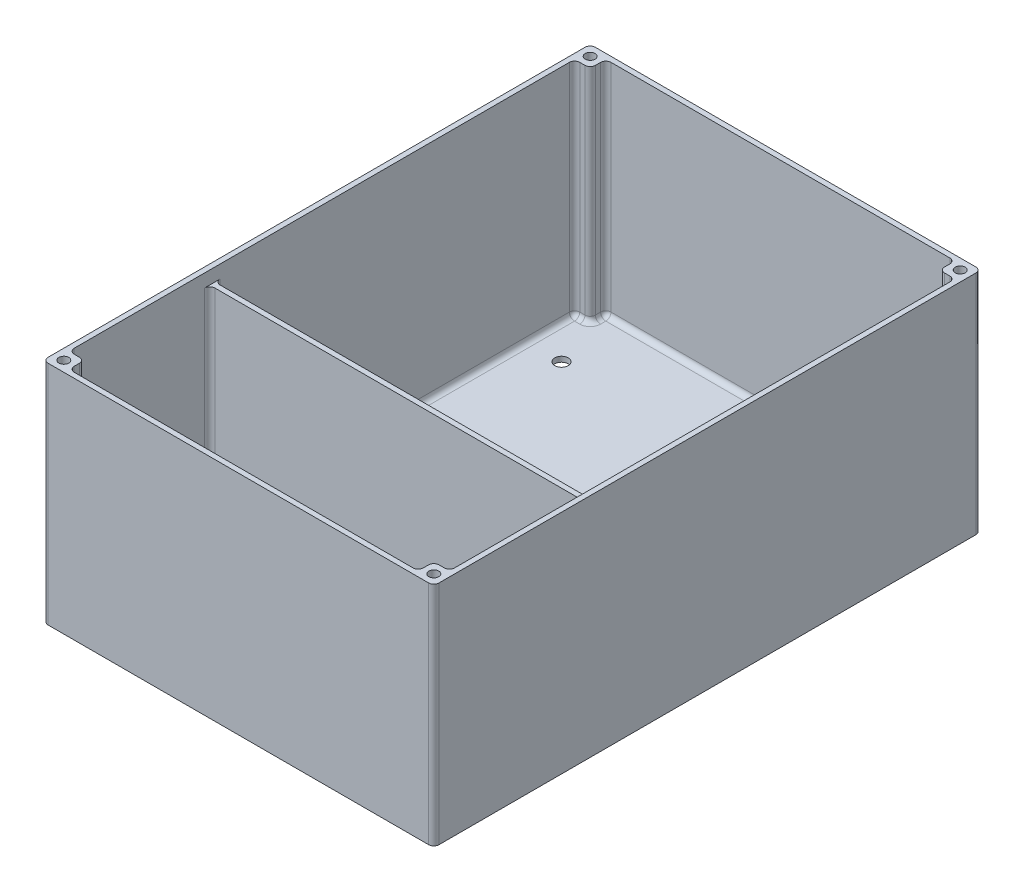
SolidWorks part; units mm, degrees
ref_plane "Front Plane" through (0, 0, 0) normal (0, 0, 1) x (1, 0, 0)
ref_plane "Top Plane" through (0, 0, 0) normal (0, 1, 0) x (1, 0, 0)
ref_plane "Right Plane" through (0, 0, 0) normal (1, 0, 0) x (0, 0, -1)
sketch "Sketch1" plane through (0, 0, 0) normal (0, 1, 0) x (1, 0, 0)
  line L1 (0, 0) -> (150, 0)
  line L2 (0, 0) -> (0, 210)
  line L3 (0, 210) -> (150, 210)
  line L4 (150, 0) -> (150, 210)
  dimension "D1" = 150
  dimension "D2" = 210
extrude "Boss-Extrude3" add sketch "Sketch1" along normal blind 2
sketch "Sketch3" plane through (0, 2, 0) normal (0, 1, 0) x (1, 0, 0)
  line L5 (0, 210) -> (150, 210)
  line L6 (0, 210) -> (0, 0)
  line L7 (0, 0) -> (150, 0)
  line L8 (2, 208) -> (2, 2)
  line L9 (2, 2) -> (148, 2)
  line L10 (148, 2) -> (148, 208)
  line L11 (148, 208) -> (2, 208)
  line L12 (2, 202) -> (2, 8)
  line L13 (8, 2) -> (142, 2)
  line L14 (148, 8) -> (148, 202)
  line L15 (142, 208) -> (8, 208)
  line L16 (150, 210) -> (150, 0)
  line L19 (2, 202) -> (8, 202)
  line L20 (8, 208) -> (8, 202)
  line L23 (148, 202) -> (142, 202)
  line L24 (142, 208) -> (142, 202)
  line L27 (2, 8) -> (8, 8)
  line L28 (8, 2) -> (8, 8)
  line L31 (148, 8) -> (142, 8)
  line L32 (142, 2) -> (142, 8)
  dimension "D2" = 6
  dimension "D1" = 2
extrude "Boss-Extrude4" add sketch "Sketch3" along normal blind 85
ref_plane "Plane1" through (75, 0, 0) normal (1, 0, 0) x (0, 0, -1)
ref_plane "Plane2" through (0, 0, -105) normal (0, 0, 1) x (1, 0, 0)
fillet "Fillet1" radius 2 16 edges at (150, 43.5, -210) (150, 43.5, 0) (0, 43.5, 0) (0, 43.5, -210) (2, 44.5, -8) (8, 44.5, -8) (8, 44.5, -2) (142, 44.5, -2) (142, 44.5, -8) (148, 44.5, -8) (148, 44.5, -202) (142, 44.5, -202) (142, 44.5, -208) (8, 44.5, -202) (8, 44.5, -208) (2, 44.5, -202)
sketch "Sketch4" plane through (0, 87, 0) normal (0, 1, 0) x (1, 0, 0)
  line L0 (4, 206) -> (4, 210) construction
  line L1 (148, 210) -> (2, 210) construction
  line L2 (4, 206) -> (0, 206) construction
  line L3 (0, 208) -> (0, 2) construction
  line L4 (75, -47.85) -> (75, 47.85) construction
  line L5 (146, 206) -> (150, 206) construction
  line L6 (146, 206) -> (146, 210) construction
  line L7 (-47.85, 105) -> (47.85, 105) construction
  line L8 (146, 4) -> (146, 0) construction
  line L9 (146, 4) -> (150, 4) construction
  line L10 (4, 4) -> (0, 4) construction
  line L11 (4, 4) -> (4, 0) construction
  circle A0 centre (4, 206) radius 1.9
  circle A1 centre (146, 206) radius 1.9
  circle A2 centre (146, 4) radius 1.9
  circle A3 centre (4, 4) radius 1.9
  dimension "D3" = 3.8
  dimension "D1" = 4
  dimension "D2" = 4
extrude "Cut-Extrude1" cut sketch "Sketch4" against normal blind 10
sketch "Sketch5" plane through (0, 2, 0) normal (0, 1, 0) x (1, 0, 0)
  line L0 (15, 184) -> (135, 184) construction
  line L1 (135, 184) -> (135, 76) construction
  line L2 (135, 76) -> (15, 76) construction
  line L3 (15, 76) -> (15, 184) construction
  line L5 (15, 184) -> (2, 184) construction
  line L6 (2, 200) -> (2, 10) construction
  line L7 (135, 184) -> (148, 184) construction
  line L8 (148, 10) -> (148, 200) construction
  circle A0 centre (15, 184) radius 2.6
  circle A1 centre (135, 184) radius 2.6
  circle A2 centre (135, 76) radius 2.6
  circle A3 centre (15, 76) radius 2.6
  dimension "D5" = 5.2
  dimension "D1" = 120
  dimension "D2" = 108
  dimension "D4" = 24
extrude "Cut-Extrude2" cut sketch "Sketch5" against normal blind 10
sketch "Sketch6" plane through (0, 2, 0) normal (0, 1, 0) x (1, 0, 0)
  line L0 (2, 200) -> (2, 10) construction
  line L1 (2, 64) -> (148, 64)
  line L2 (2, 64) -> (2, 62)
  line L3 (2, 62) -> (148, 62)
  line L4 (148, 64) -> (148, 62)
  line L5 (148, 10) -> (148, 200) construction
  line L6 (10, 2) -> (140, 2) construction
  dimension "D1" = 2
  dimension "D2" = 60
extrude "Boss-Extrude5" add sketch "Sketch6" along normal blind 80
fillet "Fillet2" radius 2 32 edges at (148, 2, -36) (147.4142, 2, -8.5858) (145, 2, -8) (142.5858, 2, -7.4142) (142, 2, -5) (141.4142, 2, -2.5858) (75, 2, -2) (8.5858, 2, -2.5858) (8, 2, -5) (7.4142, 2, -7.4142) (5, 2, -8) (2.5858, 2, -8.5858) (148, 2, -132) (147.4142, 2, -201.4142) (145, 2, -202) (142.5858, 2, -202.5858) (142, 2, -205) (141.4142, 2, -207.4142) (75, 2, -208) (8.5858, 2, -207.4142) (8, 2, -205) (7.4142, 2, -202.5858) (5, 2, -202) (2.5858, 2, -201.4142) (2, 2, -36) (2, 42, -62) (75, 2, -62) (148, 42, -62) (148, 42, -64) (2, 42, -64) (75, 2, -64) (2, 2, -132)
